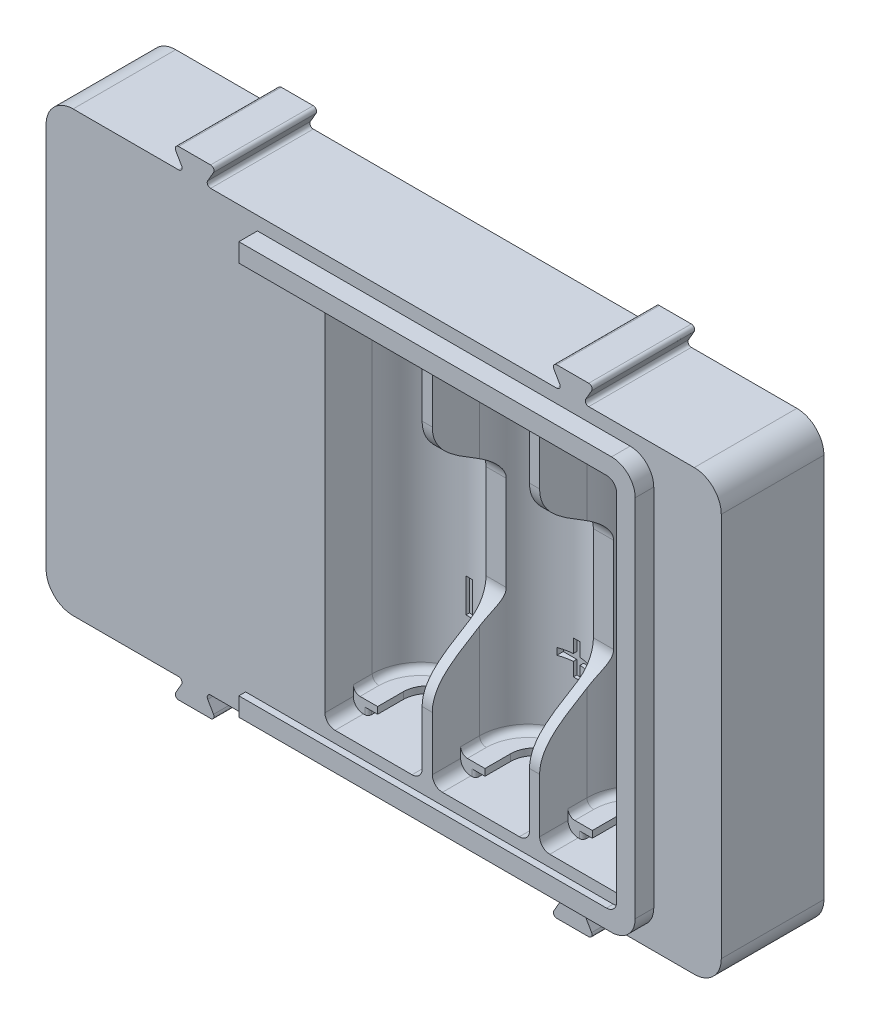
SolidWorks part; units mm, degrees
material "ABS"
ref_plane "Front Plane" through (0, 0, 0) normal (0, 0, 1) x (1, 0, 0)
ref_plane "Top Plane" through (0, 0, 0) normal (0, 1, 0) x (1, 0, 0)
ref_plane "Right Plane" through (0, 0, 0) normal (1, 0, 0) x (0, 0, -1)
sketch "Sketch1" plane through (0, 0, 0) normal (0, 1, 0) x (1, 0, 0)
  line L0 (-24.6, 0) -> (24.6, 0)
  line L1 (0, 0) -> (0, -8.2) construction
  line L2 (-5.4908, -1) -> (5.6475, -1) construction
  line L3 (7, -12.213) -> (7, -2.6204) construction
  line L4 (8.9, -12.0066) -> (8.9, -2.0587) construction
  line L5 (0, -8.2) -> (15.9, -8.2) construction
  line L6 (7.2, -8.2) -> (7.2, -15.2)
  line L7 (8.7, -8.2) -> (8.7, -15.2)
  line L8 (8.7, -15.2) -> (23.1, -15.2) construction
  line L9 (8.7, -15.2) -> (7.2, -15.2)
  line L10 (-1.7094, -15.2) -> (7.2, -15.2) construction
  line L11 (15.9, -8.2) -> (23.1, -8.2) construction
  line L12 (23.1, -15.2) -> (23.1, -8.2)
  line L13 (23.1, -15.2) -> (24.6, -15.2)
  line L14 (24.6, -15.2) -> (24.6, 0)
  line L15 (-24.6, -15.2) -> (-24.6, 0)
  line L16 (-23.1, -15.2) -> (-24.6, -15.2)
  line L17 (-23.1, -15.2) -> (-23.1, -8.2)
  line L18 (-8.7, -8.2) -> (-8.7, -15.2)
  line L19 (-8.7, -15.2) -> (-7.2, -15.2)
  line L20 (-7.2, -8.2) -> (-7.2, -15.2)
  circle A0 centre (0, -8.2) radius 7 construction
  arc A1 (-7.2, -8.2) -> (7.2, -8.2) centre (0, -8.2) cw
  circle A2 centre (15.9, -8.2) radius 7 construction
  arc A3 (8.7, -8.2) -> (23.1, -8.2) centre (15.9, -8.2) cw
  arc A4 (-8.7, -8.2) -> (-23.1, -8.2) centre (-15.9, -8.2) ccw
  dimension "D1" = 14
  dimension "D2" = 0.2
  dimension "D3" = 1
  dimension "D4" = 1.5
  dimension "D5" = 15.2
  dimension "D6" = 15.9
extrude "Boss-Extrude1" add sketch "Sketch1" along normal blind 27.8
sketch "Sketch2" plane through (0, 27.8, 0) normal (0, -1, 0) x (1, 0, 0)
  line L1 (-24.6, 15.2) -> (24.6, 15.2)
  line L2 (-24.6, 15.2) -> (-24.6, 0)
  line L3 (-24.6, 0) -> (24.6, 0)
  line L4 (24.6, 15.2) -> (24.6, 0)
extrude "Boss-Extrude2" add sketch "Sketch2" against normal blind 1.5
ref_plane "Plane1" through (-15.9, 0, 0) normal (1, 0, 0) x (0, 0, -1)
ref_plane "Plane3" through (15.9, 0, 0) normal (1, 0, 0) x (0, 0, -1)
sketch "Sketch6" plane through (0, 0, 0) normal (1, 0, 0) x (0, 0, -1)
  line L0 (-5, 0) -> (-15.2, 0)
  line L1 (-15.2, 0) -> (0, 0) construction
  line L2 (-15.2, 0) -> (-15.2, 18.3)
  line L3 (-15.2, 29.3) -> (-15.2, 0) construction
  line L4 (-5, 0) -> (-5, 7)
  line L5 (0, 29.3) -> (0, 0) construction
  line L6 (0, 29.3) -> (-15.2, 29.3) construction
  spline S0 degree 3 poles (-15.2, 18.3) (-15.2, 12.3) (-5, 11) (-5, 7) knots 0 0 0 0 1 1 1 1
  dimension "D4" = 12
  dimension "D5" = 18
  dimension "D1" = 7
  dimension "D2" = 5
  dimension "D3" = 11
extrude "Cut-Extrude2" cut sketch "Sketch6" against normal blind 15 and the other way blind 15
sketch "Sketch3" plane through (0, 27.8, 0) normal (0, -1, 0) x (1, 0, 0)
  line L0 (-10.4, 11) -> (-8.7, 11)
  line L1 (-8.7, 8.2) -> (-8.7, 15.2) construction
  line L2 (-8.7, 11) -> (-8.7, 0)
  line L3 (24.6, 0) -> (-24.6, 0) construction
  line L4 (-8.7, 0) -> (-23.1, 0)
  line L6 (-20.4, 2.9) -> (-11.4, 2.9)
  line L7 (-10.9, 3.4) -> (-10.9, 10.5)
  line L8 (-15.9, 15.2) -> (-15.9, 0) construction
  line L9 (-8.7, 15.2) -> (-23.1, 15.2) construction
  line L19 (-23.1, 11) -> (-23.1, 0)
  line L20 (-21.4, 11) -> (-23.1, 11)
  line L21 (-20.9, 3.4) -> (-20.9, 10.5)
  arc A1 (-11.4, 2.9) -> (-10.9, 3.4) centre (-11.4, 3.4) ccw
  arc A4 (-10.4, 11) -> (-10.9, 10.5) centre (-10.4, 10.5) ccw
  arc A6 (-20.4, 2.9) -> (-20.9, 3.4) centre (-20.4, 3.4) cw
  arc A7 (-21.4, 11) -> (-20.9, 10.5) centre (-21.4, 10.5) cw
  dimension "D6" = 0.5
  dimension "D7" = 0.5
  dimension "D1" = 5
  dimension "D2" = 11
  dimension "D3" = 2.9
extrude "Inner" add sketch "Sketch3" along normal blind 1
sketch "Sketch4" plane through (0, 26.8, 0) normal (0, -1, 0) x (1, 0, 0)
  line L1 (-8.7, 8.2) -> (-8.7, 15.2) construction
  line L2 (-8.7, 11) -> (-8.7, 0)
  line L3 (24.6, 0) -> (-24.6, 0) construction
  line L4 (-8.7, 0) -> (-23.1, 0)
  line L5 (-23.1, 0) -> (-23.1, 11)
  line L6 (-8.7, 11) -> (-10.4, 11) construction
  line L7 (-23.1, 11) -> (-19.5, 11)
  line L8 (-19.5, 11) -> (-19.5, 7.2)
  line L10 (-12.3, 7.2) -> (-12.3, 11)
  line L11 (-12.3, 11) -> (-8.7, 11)
  arc A0 (-19.5, 7.2) -> (-12.3, 7.2) centre (-15.9, 7.2) ccw
  dimension "D1" = 3.6
  dimension "D2" = 3.8
extrude "Boss-Extrude4" add sketch "Sketch4" along normal blind 1
sketch "Sketch5" plane through (0, 0, 15.2) normal (0, 0, 1) x (1, 0, 0)
  line L0 (-8.7, 27.8) -> (-23.1, 27.8) construction
  line L1 (-17.6, 27.8) -> (-14.2, 27.8)
  line L2 (-17.6, 27.8) -> (-17.6, 27.3)
  line L3 (-17.6, 27.3) -> (-14.2, 27.3)
  line L4 (-14.2, 27.8) -> (-14.2, 27.3)
  point P10 (-15.9, 27.8)
  dimension "D1" = 0.5
  dimension "D2" = 3.4
extrude "Cut-Extrude1" cut sketch "Sketch5" against normal through all
sketch "Sketch10" plane through (0, 0, 0) normal (0, 0, 1) x (1, 0, 0)
  line L0 (-24.6, 29.3) -> (24.6, 29.3) construction
  line L1 (-14.2, 27.3) -> (-17.6, 27.3)
  line L2 (-14.2, 27.3) -> (-14.2, 29.3)
  line L3 (-14.2, 29.3) -> (-17.6, 29.3)
  line L4 (-17.6, 27.3) -> (-17.6, 29.3)
extrude "Cut-Extrude6" cut sketch "Sketch10" along normal blind 0.6
mirror "Mirror1" about plane through (0, 0, 0) normal (1, 0, 0) of "Cut-Extrude6", "Inner", "Boss-Extrude4", "Cut-Extrude1"
ref_plane "Plane2" through (-7.95, 0, 0) normal (1, 0, 0) x (0, 0, -1)
mirror "Mirror2" about plane through (-7.95, 0, 0) normal (1, 0, 0) of "Cut-Extrude6", "Inner", "Boss-Extrude4", "Cut-Extrude1"
fillet "Fillet2" radius 1.5 6 edges at (-8.7, 27.8, 13.1) (-23.1, 27.8, 13.1) (8.7, 27.8, 13.1) (23.1, 27.8, 13.1) (7.2, 27.8, 13.1) (-7.2, 27.8, 13.1)
fillet "Fillet3" radius 1 9 edges at (-8.7, 25.8, 9.6) (-15.9, 25.8, 1) (-23.1, 25.8, 9.6) (23.1, 25.8, 9.6) (8.7, 25.8, 9.6) (7.2, 25.8, 9.6) (-7.2, 25.8, 9.6) (15.9, 25.8, 1) (0, 25.8, 1)
mirror "Mirror4" about plane through (0, 0, 0) normal (0, 1, 0) of bodies 108 110
sketch "Эскиз1" plane through (0, 0, 0) normal (0, 0, -1) x (-1, 0, 0)
  line L0 (-24.6, 29.3) -> (-24.6, -29.3) construction
  line L5 (-35.6, 32.5) -> (64.4, 32.5)
  line L6 (-35.6, 32.5) -> (-35.6, -32.5)
  line L7 (-35.6, -32.5) -> (64.4, -32.5)
  line L8 (64.4, 32.5) -> (64.4, -32.5)
  line L9 (-35.6, 32.5) -> (64.4, -32.5) construction
  line L10 (-35.6, -32.5) -> (64.4, 32.5) construction
  line L11 (-34.6, -31.5) -> (63.4, -31.5)
  line L12 (-34.6, -31.5) -> (-34.6, 31.5)
  line L13 (-34.6, 31.5) -> (63.4, 31.5)
  line L14 (63.4, -31.5) -> (63.4, 31.5)
  line L15 (-34.6, -31.5) -> (63.4, 31.5) construction
  line L16 (-34.6, 31.5) -> (63.4, -31.5) construction
  line L17 (24.6, 29.3) -> (24.6, -29.3) construction
  line L18 (-24.6, 29.3) -> (24.6, 29.3)
  line L19 (-24.6, 29.3) -> (-24.6, 31.5)
  line L20 (-24.6, 31.5) -> (24.6, 31.5)
  line L21 (24.6, 29.3) -> (24.6, 31.5)
  line L22 (-24.6, -29.3) -> (24.6, -29.3)
  line L23 (-24.6, -29.3) -> (-24.6, -31.5)
  line L24 (-24.6, -31.5) -> (24.6, -31.5)
  line L25 (24.6, -29.3) -> (24.6, -31.5)
  line L27 (-24.6, 29.3) -> (-24.6, -29.3) construction
  line L28 (63.4, 31.5) -> (55.9, 31.5)
  line L29 (63.4, 31.5) -> (63.4, 24)
  line L30 (63.4, 24) -> (55.9, 24)
  line L31 (55.9, 31.5) -> (55.9, 24)
  line L32 (63.4, -31.5) -> (55.9, -31.5)
  line L33 (63.4, -31.5) -> (63.4, -24)
  line L34 (63.4, -24) -> (55.9, -24)
  line L35 (55.9, -31.5) -> (55.9, -24)
  line L36 (-34.6, 31.5) -> (-24.6, 31.5)
  line L37 (-34.6, 31.5) -> (-34.6, 24)
  line L38 (-34.6, 24) -> (-24.6, 24)
  line L39 (-24.6, 31.5) -> (-24.6, 24)
  line L41 (-34.6, -31.5) -> (-24.6, -31.5)
  line L42 (-34.6, -31.5) -> (-34.6, -24)
  line L43 (-34.6, -24) -> (-24.6, -24)
  line L44 (-24.6, -31.5) -> (-24.6, -24)
  point P0 (14.4, 0)
  point P5 (14.4, 0)
  line M16 (24.6, 29.3) -> (17.6, 29.3)
  line M20 (14.2, 29.3) -> (1.7, 29.3)
  line M24 (-1.7, 29.3) -> (-14.2, 29.3)
  line M28 (-17.6, 29.3) -> (-24.6, 29.3)
  line M30 (-24.6, 29.3) -> (-24.6, -29.3)
  dimension "D1" = 100
  dimension "D2" = 65
  dimension "D3" = 1
  dimension "D4" = 1
  dimension "D5" = 10
  dimension "D6" = 7.5
extrude "Бобышка-Вытянуть1" add sketch "Эскиз1" against normal up to surface (15.2 mm away) contours L13 L31 L30 L14 | L35 L11 L14 L34 | L43 L12 L11 L23 M30 | L12 L38 L19 L13 M30 | L8 L5 L6 L7 L14 L11 L12 L13 | L21 L13 L19 L18 M16 M28 M24 M20 | L23 L22 L25 L24 region at (-14.4, 32.3807, 0) region at (29.6, -27.75, 0) region at (29.6, 27.75, 0) region at (-59.65, -27.75, 0) region at (0, 30.4, 0) region at (-59.65, 27.75, 0) up to face at (0, 0, 15.2)
sketch "Эскиз2" plane through (0, 0, 0) normal (0, 0, -1) x (-1, 0, 0)
  line L0 (63.4, -24) -> (63.4, 24) construction
  line L1 (-34.6, -31.5) -> (63.4, -31.5)
  line L2 (-34.6, -31.5) -> (-34.6, 31.5)
  line L3 (-34.6, 31.5) -> (63.4, 31.5)
  line L4 (63.4, -31.5) -> (63.4, 31.5)
  line L5 (-34.6, -24) -> (-34.6, 24) construction
  line L6 (24.6, 31.5) -> (55.9, 31.5) construction
  line L7 (24.6, -31.5) -> (55.9, -31.5) construction
  line L11 (-34.6, 24) -> (-27.1, 24)
  line L12 (-27.1, 31.5) -> (-27.1, 24)
  line L13 (55.9, 24) -> (63.4, 24)
  line L14 (55.9, 24) -> (55.9, 31.5)
  line L17 (55.9, -24) -> (63.4, -24)
  line L18 (55.9, -24) -> (55.9, -31.5)
  line L23 (-34.6, -24) -> (-27.1, -24)
  line L24 (-27.1, -31.5) -> (-27.1, -24)
  line L25 (-27.1, 29.5) -> (55.9, 29.5)
  line L26 (-27.1, -29.5) -> (55.9, -29.5)
  line L27 (-33.6, 24) -> (-33.6, -24)
  line L28 (62.4, -24) -> (62.4, 24)
  line L29 (63.4, 24) -> (55.9, 24) construction
  line L30 (-34.6, -24) -> (-24.6, -24) construction
  line M29 (24.6, -31.5) -> (24.6, 31.5)
  dimension "D1" = 1
  dimension "D2" = 1
  dimension "D3" = 2
  dimension "D4" = 2
  dimension "D5" = 7.5
extrude "Вырез-Вытянуть5" cut sketch "Эскиз2" against normal blind 2 contours L26 L24 L1 M29 | L12 L25 L3 M29 region at (1.25, -30.5, 0) region at (1.25, 30.5, 0)
sketch "Эскиз11" plane through (0, 0, 15.2) normal (0, 0, 1) x (1, 0, 0)
  line L0 (-43.9, 32.5) -> (-45.6321, 35.5)
  line L2 (-45.6321, 35.5) -> (-39.1679, 35.5)
  line L3 (-39.1679, 35.5) -> (-40.9, 32.5)
  line L4 (-40.9, 32.5) -> (-43.9, 32.5)
  line L5 (12.1, 32.5) -> (10.3679, 35.5)
  line L6 (10.3679, 35.5) -> (16.8321, 35.5)
  line L7 (16.8321, 35.5) -> (15.1, 32.5)
  line L8 (15.1, 32.5) -> (12.1, 32.5)
  line L11 (-43.9, -32.5) -> (-45.6321, -35.5)
  line L13 (-45.6321, -35.5) -> (-39.1679, -35.5)
  line L14 (-39.1679, -35.5) -> (-40.9, -32.5)
  line L15 (-40.9, -32.5) -> (-43.9, -32.5)
  line L16 (12.1, -32.5) -> (10.3679, -35.5)
  line L17 (10.3679, -35.5) -> (16.8321, -35.5)
  line L18 (16.8321, -35.5) -> (15.1, -32.5)
  line L19 (15.1, -32.5) -> (12.1, -32.5)
  line L20 (-64.4, -32.5) -> (35.6, -32.5) construction
  line L21 (-64.4, 32.5) -> (35.6, 32.5) construction
  line L22 (-64.4, -32.5) -> (-64.4, 32.5) construction
  line L23 (35.6, -32.5) -> (35.6, 32.5) construction
  dimension "D1" = 60
  dimension "D2" = 3
  dimension "D3" = 3
  dimension "D4" = 3
  dimension "D5" = 20.5
  dimension "D6" = 20.5
  dimension "D7" = 3
extrude "Бобышка-Вытянуть3" add sketch "Эскиз11" against normal up to surface (15.2 mm away) up to face at (-15.9, 28.3, 0)
fillet "Скругление8" radius 0.5 16 edges at (-45.6321, -35.5, 7.6) (-43.9, -32.5, 7.6) (-39.1679, -35.5, 7.6) (-40.9, -32.5, 7.6) (16.8321, -35.5, 7.6) (15.1, -32.5, 7.6) (10.3679, -35.5, 7.6) (12.1, -32.5, 7.6) (15.1, 32.5, 7.6) (16.8321, 35.5, 7.6) (12.1, 32.5, 7.6) (10.3679, 35.5, 7.6) (-43.9, 32.5, 7.6) (-40.9, 32.5, 7.6) (-39.1679, 35.5, 7.6) (-45.6321, 35.5, 7.6)
sketch "Эскиз12" plane through (0, 0, 0) normal (0, 0, -1) x (-1, 0, 0)
  line L4 (-35.6, 32.5) -> (-35.6, -32.5) construction
  line L6 (64.4, 32.5) -> (64.4, -32.5) construction
  line L7 (44.766, -32.5) -> (64.4, -32.5) construction
  line L8 (-35.6, 32.5) -> (-15.966, 32.5) construction
  circle A0 centre (-31.1, 28) radius 1.9
  circle A1 centre (59.9, 28) radius 1.9
  circle A2 centre (59.9, -28) radius 1.9
  circle A3 centre (-31.1, -28) radius 1.9
  point P8 (59.9, 28)
  point P9 (59.9, -28)
  point P10 (-31.1, -28)
  point P12 (-31.1, 28)
  dimension "D1" = 3.8
  dimension "D2" = 4.5
  dimension "D3" = 4.5
  dimension "D4" = 4.5
  dimension "D5" = 4.5
extrude "Вырез-Вытянуть2" cut sketch "Эскиз12" against normal blind 5
fillet "Скругление10" radius 4 2 edges at (-55.9, 24, 7.6) (-55.9, -24, 7.6)
sketch "Эскиз13" [suppressed] plane through (0, 0, 15.2) normal (0, 0, 1) x (1, 0, 0)
  line L1 (-24.6, 31.5) -> (27.1, 31.5)
  line L2 (-24.6, 31.5) -> (-24.6, -31.5)
  line L3 (-24.6, -31.5) -> (27.1, -31.5)
  line L4 (27.1, 31.5) -> (27.1, -31.5)
  line L5 (-55.9, -31.5) -> (-24.6, -31.5) construction
  line L6 (-55.9, 31.5) -> (-24.6, 31.5) construction
  line L8 (34.6, 24) -> (34.6, -24) construction
  line L9 (-24.6, 31.5) -> (-24.6, -31.5) construction
  dimension "D1" = 7.5
extrude "Вырез-Вытянуть4" [suppressed] cut sketch "Эскиз13" against normal through all
sketch "Эскиз17" plane through (0, 0, 15.2) normal (0, 0, 1) x (1, 0, 0)
  line L0 (-40.034, -32.5) -> (11.234, -32.5) construction
  line L1 (-64.4, 32.5) -> (-24.6, 32.5)
  line L2 (-64.4, 32.5) -> (-64.4, -32.5)
  line L3 (-64.4, -32.5) -> (-24.6, -32.5)
  line L4 (-24.6, 32.5) -> (-24.6, -32.5)
  line L6 (35.6, -32.5) -> (24.6, -32.5)
  line L7 (35.6, -32.5) -> (35.6, 32.5)
  line L8 (35.6, 32.5) -> (24.6, 32.5)
  line L9 (24.6, -32.5) -> (24.6, 32.5)
  line L12 (15.966, 32.5) -> (35.6, 32.5) construction
  dimension "D1" = 39.8
  dimension "D2" = 11
extrude "Бобышка-Вытянуть4" add sketch "Эскиз17" against normal blind 1
sketch "Эскиз24" [suppressed] plane through (0, 0, 15.2) normal (0, 0, 1) x (1, 0, 0)
  line L1 (-64.4, 32.5) -> (35.6, 32.5)
  line L2 (-64.4, 32.5) -> (-64.4, -32.5)
  line L3 (-64.4, -32.5) -> (35.6, -32.5)
  line L4 (35.6, 32.5) -> (35.6, -32.5)
extrude "Бобышка-Вытянуть7" [suppressed] add sketch "Эскиз24" against normal blind 1
fillet "Скругление13" radius 4 4 edges at (-64.4, 32.5, 7.6) (35.6, 32.5, 7.6) (35.6, -32.5, 7.6) (-64.4, -32.5, 7.6)
sketch "Эскиз18" plane through (0, 0, 0) normal (0, 0, -1) x (-1, 0, 0)
  line L1 (-17.6, 27.3) -> (-14.2, 27.3)
  line L2 (-17.6, 27.3) -> (-17.6, 29.5)
  line L3 (-17.6, 29.5) -> (-14.2, 29.5)
  line L4 (-14.2, 27.3) -> (-14.2, 29.5)
  line L5 (-27.1, 29.5) -> (24.6, 29.5) construction
  line L6 (-1.7, 27.3) -> (1.7, 27.3)
  line L7 (-1.7, 27.3) -> (-1.7, 29.5)
  line L8 (-1.7, 29.5) -> (1.7, 29.5)
  line L9 (1.7, 27.3) -> (1.7, 29.5)
  line L10 (14.2, 27.3) -> (17.6, 27.3)
  line L11 (14.2, 27.3) -> (14.2, 29.5)
  line L12 (14.2, 29.5) -> (17.6, 29.5)
  line L13 (17.6, 27.3) -> (17.6, 29.5)
  line L14 (-27.1, -29.5) -> (24.6, -29.5) construction
  line L15 (14.2, -27.3) -> (17.6, -27.3)
  line L16 (14.2, -27.3) -> (14.2, -29.5)
  line L17 (14.2, -29.5) -> (17.6, -29.5)
  line L18 (17.6, -27.3) -> (17.6, -29.5)
  line L19 (-27.1, -29.5) -> (24.6, -29.5) construction
  line L20 (-1.7, -27.3) -> (1.7, -27.3)
  line L21 (-1.7, -27.3) -> (-1.7, -29.5)
  line L22 (-1.7, -29.5) -> (1.7, -29.5)
  line L23 (1.7, -27.3) -> (1.7, -29.5)
  line L24 (-17.6, -27.3) -> (-14.2, -27.3)
  line L25 (-17.6, -27.3) -> (-17.6, -29.5)
  line L26 (-17.6, -29.5) -> (-14.2, -29.5)
  line L27 (-14.2, -27.3) -> (-14.2, -29.5)
  line L28 (1.7, -27.3) -> (1.7, -29.3) construction
  line L29 (-14.2, -27.3) -> (-14.2, -29.3) construction
  line L30 (17.6, -29.3) -> (17.6, -27.3) construction
  line L31 (17.6, 29.3) -> (17.6, 27.8) construction
  line L32 (1.7, 27.8) -> (1.7, 29.3) construction
  line L33 (-14.2, 27.8) -> (-14.2, 29.3) construction
  line L35 (-27.1, 29.5) -> (24.6, 29.5) construction
  line L36 (-27.1, 29.5) -> (24.6, 29.5) construction
extrude "Вырез-Вытянуть6" cut sketch "Эскиз18" against normal up to surface (2 mm away) up to face at (1.25, -30.5, 2)
sketch "Эскиз20" plane through (0, 0, 15.2) normal (0, 0, 1) x (1, 0, 0)
  line L0 (-64.4, -28.5) -> (-64.4, 28.5) construction
  line L5 (-18.4, 15.5) -> (-13.4, 15.5)
  line L6 (-18.4, 15.5) -> (-18.4, 14.5)
  line L7 (-18.4, 14.5) -> (-13.4, 14.5)
  line L8 (-13.4, 15.5) -> (-13.4, 14.5)
  line L9 (-18.4, 15.5) -> (-13.4, 14.5) construction
  line L10 (-18.4, 14.5) -> (-13.4, 15.5) construction
  line L11 (-16.4, 17.5) -> (-15.4, 17.5)
  line L12 (-16.4, 17.5) -> (-16.4, 12.5)
  line L13 (-16.4, 12.5) -> (-15.4, 12.5)
  line L14 (-15.4, 17.5) -> (-15.4, 12.5)
  line L15 (-16.4, 17.5) -> (-15.4, 12.5) construction
  line L16 (-16.4, 12.5) -> (-15.4, 17.5) construction
  line L17 (-16.4, -12.5) -> (-15.4, -12.5)
  line L18 (-16.4, -12.5) -> (-16.4, -17.5)
  line L19 (-16.4, -17.5) -> (-15.4, -17.5)
  line L20 (-15.4, -12.5) -> (-15.4, -17.5)
  line L21 (-16.4, -12.5) -> (-15.4, -17.5) construction
  line L22 (-16.4, -17.5) -> (-15.4, -12.5) construction
  line L23 (-10.2, 27.8) -> (-21.6, 27.8) construction
  line L24 (5.7, 27.8) -> (-5.7, 27.8) construction
  line L25 (21.6, 27.8) -> (10.2, 27.8) construction
  line L43 (-0.5, 12.5) -> (0.5, 12.5)
  line L44 (-0.5, 12.5) -> (-0.5, 17.5)
  line L45 (-0.5, 17.5) -> (0.5, 17.5)
  line L46 (0.5, 12.5) -> (0.5, 17.5)
  line L47 (-0.5, 12.5) -> (0.5, 17.5) construction
  line L48 (-0.5, 17.5) -> (0.5, 12.5) construction
  line L49 (15.4, 12.5) -> (16.4, 12.5)
  line L50 (15.4, 12.5) -> (15.4, 17.5)
  line L51 (15.4, 17.5) -> (16.4, 17.5)
  line L52 (16.4, 12.5) -> (16.4, 17.5)
  line L53 (15.4, 12.5) -> (16.4, 17.5) construction
  line L54 (15.4, 17.5) -> (16.4, 12.5) construction
  line L55 (15.4, -17.5) -> (16.4, -17.5)
  line L56 (15.4, -17.5) -> (15.4, -12.5)
  line L57 (15.4, -12.5) -> (16.4, -12.5)
  line L58 (16.4, -17.5) -> (16.4, -12.5)
  line L59 (15.4, -17.5) -> (16.4, -12.5) construction
  line L60 (15.4, -12.5) -> (16.4, -17.5) construction
  line L61 (-0.5, -17.5) -> (0.5, -17.5)
  line L62 (-0.5, -17.5) -> (-0.5, -12.5)
  line L63 (-0.5, -12.5) -> (0.5, -12.5)
  line L64 (0.5, -17.5) -> (0.5, -12.5)
  line L65 (-0.5, -17.5) -> (0.5, -12.5) construction
  line L66 (-0.5, -12.5) -> (0.5, -17.5) construction
  line L67 (13.4, 14.5) -> (18.4, 14.5)
  line L68 (13.4, 14.5) -> (13.4, 15.5)
  line L69 (13.4, 15.5) -> (18.4, 15.5)
  line L70 (18.4, 14.5) -> (18.4, 15.5)
  line L71 (13.4, 14.5) -> (18.4, 15.5) construction
  line L72 (13.4, 15.5) -> (18.4, 14.5) construction
  line L73 (-2.5, -15.5) -> (2.5, -15.5)
  line L74 (-2.5, -15.5) -> (-2.5, -14.5)
  line L75 (-2.5, -14.5) -> (2.5, -14.5)
  line L76 (2.5, -15.5) -> (2.5, -14.5)
  line L77 (-2.5, -15.5) -> (2.5, -14.5) construction
  line L78 (-2.5, -14.5) -> (2.5, -15.5) construction
  point P0 (-15.9, -15)
  point P4 (-15.9, 15)
  point P9 (-15.9, 15)
  point P15 (15.9, 27.8)
  point P16 (-15.9, 27.8)
  point P17 (0, 15)
  point P18 (-15.9, 0)
  point P22 (-64.4, 0)
  point P24 (0, 27.8)
  point P33 (15.9, 15)
  point P38 (15.9, -15)
  point P43 (0, -15)
  point P48 (0, -15)
  point P52 (15.9, 15)
  dimension "D1" = 1
  dimension "D2" = 5
  dimension "D3" = 15
  dimension "D4" = 15
extrude "Вырез-Вытянуть8" cut sketch "Эскиз20" against normal blind 14.7 contours L5 L8 L7 L6 | L14 L13 L12 L11 | L46 L45 L44 L43 | L69 L70 L67 L68 | L50 L51 L52 L49 | L56 L57 L58 L55 | L75 L76 L73 L74 | L62 L63 L64 L61 | L20 L19 L18 L17
sketch "Эскиз22" plane through (0, 0, 15.2) normal (0, 0, 1) x (1, 0, 0)
  line L0 (23.1, 24.8) -> (23.1, -24.8) construction
  line L1 (-33.1, 29.5) -> (24.6, 29.5)
  line L3 (-33.1, -29.5) -> (24.6, -29.5)
  line L4 (24.6, 29.5) -> (24.6, -29.5)
  line L8 (-33.1, -29.5) -> (-33.1, -30.5)
  line L9 (-33.1, 30.5) -> (25.6, 30.5)
  line L10 (-33.1, 30.5) -> (-33.1, 29.5)
  line L11 (-33.1, -30.5) -> (25.6, -30.5)
  line L12 (25.6, 30.5) -> (25.6, -30.5)
  line L13 (-23.1, 26.3) -> (-23.1, -26.3) construction
  dimension "D1" = 1.5
  dimension "D2" = 29.5
  dimension "D3" = 29.5
  dimension "D4" = 10
  dimension "D5" = 1
  dimension "D6" = 1
  dimension "D7" = 1
extrude "Бобышка-Вытянуть5" add sketch "Эскиз22" along normal blind 1.75
sketch "Эскиз23" plane through (0, 0, 16.95) normal (0, 0, 1) x (1, 0, 0)
  line L0 (-33.1, 30.5) -> (-33.1, 27.75)
  line L1 (-33.1, 27.75) -> (22.85, 27.75)
  line L2 (22.85, 27.75) -> (22.85, -27.75)
  line L3 (22.85, -27.75) -> (-33.1, -27.75)
  line L4 (-33.1, -27.75) -> (-33.1, -30.5)
  line L5 (-33.1, -30.5) -> (25.6, -30.5)
  line L6 (25.6, -30.5) -> (25.6, 30.5)
  line L7 (25.6, 30.5) -> (-33.1, 30.5)
  dimension "D1" = 2.75
  dimension "D2" = 2.75
  dimension "D3" = 2.75
extrude "Бобышка-Вытянуть6" add sketch "Эскиз23" along normal blind 1
fillet "Скругление14" radius 2.5 2 edges at (24.6, -29.5, 16.075) (24.6, 29.5, 16.075)
fillet "Скругление15" radius 3.5 2 edges at (25.6, -30.5, 16.575) (25.6, 30.5, 16.575)
fillet "Скругление16" radius 1.5 2 edges at (22.85, -27.75, 17.45) (22.85, 27.75, 17.45)
fillet "Скругление17" [suppressed] radius 4
